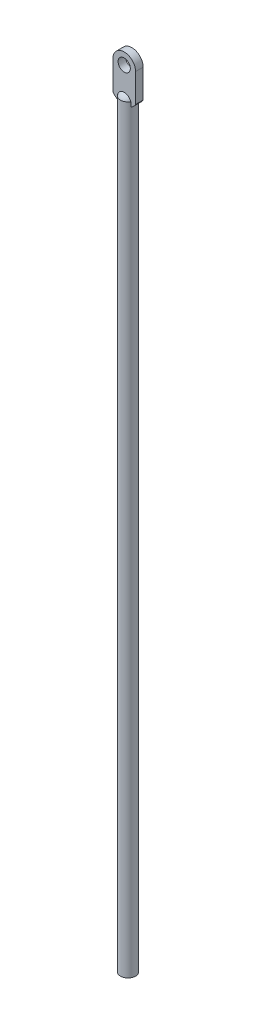
SolidWorks part; units mm, degrees
material "PW100:Mi:0:3:C1:0:1:2:Re:26:"
ref_plane "Front" through (0, 0, 0) normal (0, 0, 1) x (1, 0, 0)
ref_plane "Top" through (0, 0, 0) normal (0, 1, 0) x (1, 0, 0)
ref_plane "Right" through (0, 0, 0) normal (1, 0, 0) x (0, 0, -1)
sketch "Support-Front" plane through (0, 0, 0) normal (0, 0, 1) x (1, 0, 0)
  line L3 (5, 496.1634) -> (-5, 496.1634) construction
  line L4 (5, 515) -> (-5, 515)
  line L5 (7.5, 496.1634) -> (7.5, 515)
  line L6 (7.5, 496.1634) -> (-7.5, 496.1634) construction
  line L11 (-7.5, 515) -> (-7.5, 496.1634)
  line L12 (5, -5) -> (-5, -5)
  line L14 (-5, 496.1634) -> (5, 493.4839) construction
  line L19 (5, 0) -> (-5, 0) construction
  line L20 (-5, 0) -> (0, -5) construction
  line L22 (-7.5, 496.1634) -> (7.5, 496.1634)
  line L23 (5, 515) -> (5, -5)
  line L29 (-5, 515) -> (-5, -5)
  line L37 (0, -5) -> (0, 522.5) construction
  arc A0 (7.5, 496.1634) -> (-7.5, 496.1634) centre (0, 500.6549) cw
  arc A7 (7.5, 515) -> (-7.5, 515) centre (0, 515) ccw
  circle A8 centre (0, 515) radius 4.05
  arc A9 (5, 496.1634) -> (-5, 496.1634) centre (0, 494.8236) ccw
  point P1 (0, 0)
  dimension "Diam-Hole-Clevis" = 8.1
  dimension "D1" = 45
  dimension "D2" = 15
  dimension "Diam-Piston-Rod" = 10
  dimension "Height-Clevis" = 15
  dimension "Dist-End-Fitting-Rod" = 15
  dimension "Piston_Rod_Length" = 500
sketch "Support-Right" plane through (0, 0, 0) normal (1, 0, 0) x (0, 0, -1)
  line L1 (2.5, 522.5) -> (-2.5, 522.5)
  line L2 (2.5, 522.5) -> (2.5, 496.1634)
  line L3 (2.5, 496.1634) -> (-2.5, 496.1634)
  line L4 (-2.5, 522.5) -> (-2.5, 496.1634)
  dimension "Width-Clevis" = 5
ref_axis "Ref-Axis-Center" through (0, 522.5, 0) along (0, -1, 0)
ref_plane "Ref-Plane-Cylinder-Front" through (0, 493.4839, 0) normal (0, 1, 0) x (-1, 0, 0)
ref_plane "Ref-Plane-Front" through (0, 0, 0) normal (0, 0, 1) x (1, 0, 0)
ref_plane "Ref-Plane-Clevis-Front" through (0, 0, -2.5) normal (0, 0, 1) x (1, 0, 0)
ref_plane "Ref-Plane-Clevis-End" through (0, 0, 2.5) normal (0, 0, 1) x (1, 0, 0)
ref_plane "Ref-Plane-Insert" through (0, 0, 0) normal (0, 1, 0) x (-1, 0, 0)
sketch "Sketch5" plane through (0, 0, 0) normal (0, 0, 1) x (1, 0, 0)
  line L0 (5, 515) -> (5, -5) construction
  line L1 (5, 496.1634) -> (5, -5)
  line L6 (0, -5) -> (0, 522.5) construction
  line L9 (0, -5) -> (0, 500)
  line L13 (5, -5) -> (0, -5)
  line L22 (0, -5) -> (0, 522.5) construction
  arc A1 (5, 496.1634) -> (-5, 496.1634) centre (0, 494.8236) ccw construction
  arc A2 (5, 496.1634) -> (0, 500) centre (0, 494.8236) ccw
revolve "Body" add sketch "Sketch5" angle 360 about L6
sketch "Sketch6" plane through (0, 0, -2.5) normal (0, 0, 1) x (1, 0, 0)
  line L0 (-7.5, 515) -> (-7.5, 496.1634) construction
  line L1 (7.5, 496.1634) -> (7.5, 515) construction
  line L2 (-7.5, 515) -> (-7.5, 496.1634)
  line L3 (7.5, 496.1634) -> (7.5, 515)
  arc A1 (7.5, 515) -> (-7.5, 515) centre (0, 515) ccw construction
  arc A2 (7.5, 515) -> (-7.5, 515) centre (0, 515) ccw
  arc A3 (-7.5, 496.1634) -> (7.5, 496.1634) centre (0, 500.6549) ccw construction
  arc A4 (-7.5, 496.1634) -> (7.5, 496.1634) centre (0, 500.6549) ccw
  circle A6 centre (0, 515) radius 4.05 construction
  circle A7 centre (0, 515) radius 4.05
extrude "Clevis" add sketch "Sketch6" against normal up to surface (-5 mm away) up to plane "Ref-Plane-Clevis-End"
ref_axis "Ref-Axis-End-Fitting" through (0, 515, 31.7521) along (0, 0, -1)
ref_plane "Ref-Plane-End-Fitting" through (0, 515, 0) normal (0, 1, 0) x (-1, 0, 0)
equation "\"Thickness-Plate-Thread@Support-Front\" = \"Length-Thread@Support-Front\" / 5"
equation "\"Pitch@Thread-Simple\" = \"Pitch-Thread@Support-Thread\""
equation "\"Width-Thread-Bottom@Support-Thread\" = \"Pitch-Thread@Support-Thread\" / 4"
equation "\"Width-Thread-Top@Support-Thread\" = \"Pitch-Thread@Support-Thread\" / 8"
equation "\"Pitch@Thread-Simple\" = \"Pitch-Thread@Support-Thread\" "
equation "\"Num-Thread@Thread-Simple\" = INT(\"Length-Thread@Support-Front\" / \"Pitch-Thread@Support-Thread\" +1)"
